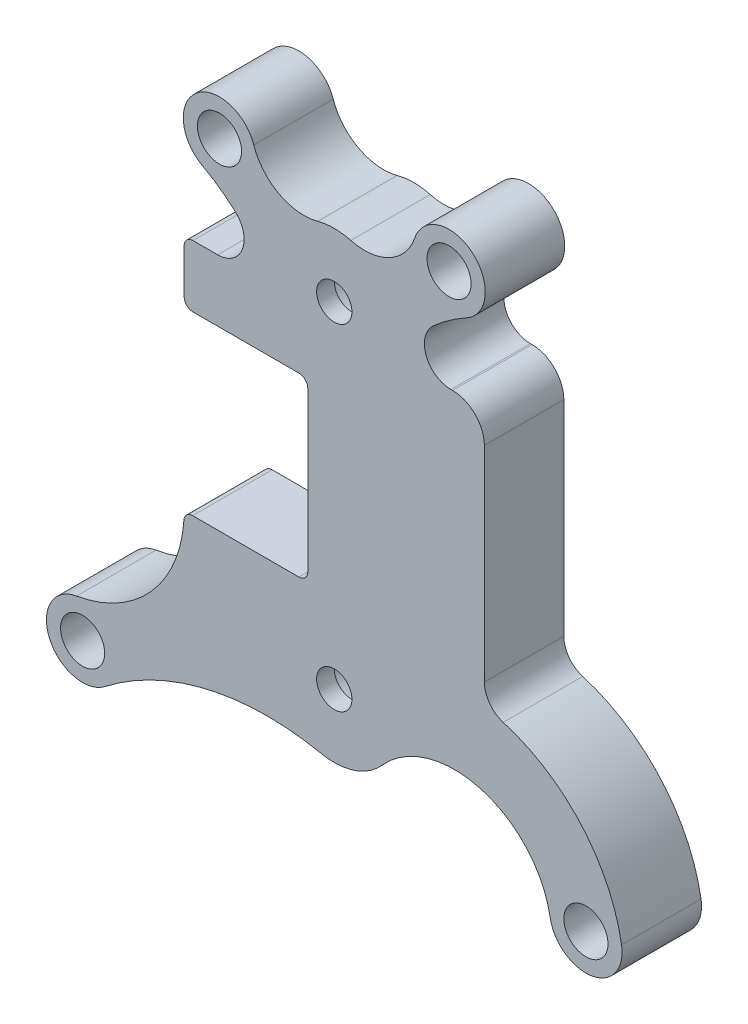
SolidWorks part; units mm, degrees
material "Полиамид ПА-6Б ТУ 6-05-988-87"
ref_plane "Спереди" through (0, 0, 0) normal (0, 0, 1) x (1, 0, 0)
ref_plane "Сверху" through (0, 0, 0) normal (0, 1, 0) x (1, 0, 0)
ref_plane "Справа" through (0, 0, 0) normal (1, 0, 0) x (0, 0, -1)
sketch "Эскиз1" plane through (0, 0, 0) normal (0, 0, 1) x (1, 0, 0)
  line L0 (0, 0) -> (17.2556, 0) construction
  line L1 (0, 0) -> (0, -0.75) construction
  line L2 (11.0974, -0.75) -> (-16.0026, -0.75) construction
  line L3 (-8.5, 8.5) -> (-2.75, 8.5) construction
  line L4 (-2, -5) -> (-8.016, -5)
  line L5 (-1.5, -4.5) -> (-1.5, 4.5)
  line L6 (-2, 5) -> (-8, 5)
  line L10 (-8, 8.5) -> (-6.6051, 8.5)
  line L11 (-8.5, 8) -> (-8.5, 5.5)
  line L13 (8.5, 6.7) -> (8.5, -4.9039)
  line L14 (6.0474, 13.15) -> (-10.9526, 13.15) construction
  line L16 (6.6051, 8.5) -> (6.7, 8.5)
  line L17 (0, 0) -> (-7.145, 0) construction
  arc A0 (7.4857, 12.4525) -> (4.5587, 14.9087) centre (6.5, 14.25) ccw
  circle A1 centre (6.5, 14.25) radius 1.25
  circle A2 centre (-6.5, 14.25) radius 1.25
  circle A3 centre (0, -9.5) radius 1
  arc A4 (-4.5587, 14.9087) -> (-7.4857, 12.4525) centre (-6.5, 14.25) ccw
  arc A5 (-14.5962, -12.2294) -> (-12.9918, -15.8684) centre (-14.25, -14.25) ccw
  circle A6 centre (-14.25, -14.25) radius 1.25
  circle A7 centre (14.25, -14.25) radius 1.25
  arc A8 (12.2299, -14.5991) -> (16.2701, -13.9009) centre (14.25, -14.25) ccw
  circle A9 centre (0, 9.5) radius 2 construction
  circle A10 centre (0, 9.5) radius 1
  arc A11 (0.937, 12.9759) -> (-0.937, 12.9759) centre (0, 9.5) ccw
  arc A12 (-4.5587, 14.9087) -> (-0.937, 12.9759) centre (-1.7178, 15.8725) ccw
  arc A13 (-7.4857, 12.4525) -> (-5.6012, 11.1145) centre (-12.2938, 3.6843) cw
  circle A14 centre (0, -9.5) radius 2 construction
  arc A15 (7.4857, 12.4525) -> (5.6012, 11.1145) centre (12.2938, 3.6843) ccw
  arc A16 (4.5587, 14.9087) -> (0.937, 12.9759) centre (1.7178, 15.8725) cw
  arc A17 (2.6942, -11.8878) -> (-0.7326, -13.0247) centre (0, -9.5) cw
  arc A18 (6.6051, 8.5) -> (5.6012, 11.1145) centre (6.6051, 10) cw
  arc A19 (2.6942, -11.8878) -> (12.2299, -14.5991) centre (6.8103, -15.5357) cw
  arc A20 (-6.6051, 8.5) -> (-5.6012, 11.1145) centre (-6.6051, 10) ccw
  arc A21 (16.2701, -13.9009) -> (9.569, -6.3406) centre (6.8103, -15.5357) ccw
  arc A22 (9.569, -6.3406) -> (8.5, -4.9039) centre (10, -4.9039) cw
  arc A23 (-12.9918, -15.8684) -> (-0.7326, -13.0247) centre (-3.7853, -27.7108) cw
  arc A24 (-14.5962, -12.2294) -> (-8.515, -5.4681) centre (-15.8348, -5) ccw
  arc A25 (-8, 8.5) -> (-8.5, 8) centre (-8, 8) ccw
  arc A26 (-8.515, -5.4681) -> (-8.016, -5) centre (-8.016, -5.5) cw
  arc A27 (-2, -5) -> (-1.5, -4.5) centre (-2, -4.5) ccw
  arc A28 (-1.5, 4.5) -> (-2, 5) centre (-2, 4.5) ccw
  arc A29 (-8, 5) -> (-8.5, 5.5) centre (-8, 5.5) cw
  arc A30 (6.7, 8.5) -> (8.5, 6.7) centre (6.7, 6.7) cw
  point P1 (-1.5, 0)
  point P20 (-8.5, 8.5)
  point P43 (-7.145, 0)
  point P44 (-8.5, -5)
  dimension "D1" = 2.5
  dimension "D2" = 0.8
  dimension "D3" = 4
  dimension "D4" = 2
  dimension "D5" = 1.6
  dimension "D6" = 3
  dimension "D7" = 10
  dimension "D8" = 5.5
  dimension "D11" = 1.5
  dimension "D12" = 15
  dimension "D13" = 8.5
  dimension "D14" = 0.5
  dimension "D15" = 1.8
  dimension "D9" = 10
  dimension "D10" = 1.5
extrude "Бобышка-Вытянуть3" add sketch "Эскиз1" along normal blind 4.5
sketch "Эскиз3" plane through (0, 0, 0) normal (0, 0, -1) x (-1, 0, 0)
  circle A0 centre (0, -9.5) radius 2 construction
  circle A1 centre (0, 9.5) radius 2 construction
  circle A2 centre (0, -9.5) radius 2
  circle A3 centre (0, 9.5) radius 2
extrude "Вырез-Вытянуть2" cut sketch "Эскиз3" against normal offset from surface (3.5 mm away) 1 up to face at (1, 9.5, 4.5)
sketch "Эскиз4" plane through (0, 0, 0) normal (0, 0, -1) x (-1, 0, 0)
  line L0 (6.35, -8.95) -> (4.55, -8.95)
  line L1 (-0.95, -3.0841) -> (-0.95, -16.25)
  line L2 (-0.95, -16.25) -> (6.35, -16.25)
  line L3 (6.35, -16.25) -> (6.35, -8.95)
  line L4 (5.35, -15.25) -> (5.35, -9.95)
  line L5 (0.05, -15.25) -> (5.35, -15.25)
  line L6 (0.05, -9.95) -> (0.05, -15.25)
  line L7 (5.35, -9.95) -> (0.05, -9.95)
  line L8 (5.35, -15.25) -> (5.35, -9.95) construction
  line L9 (0.05, -15.25) -> (5.35, -15.25) construction
  line L10 (0.05, -9.95) -> (0.05, -15.25) construction
  line L11 (5.35, -9.95) -> (0.05, -9.95) construction
  line L13 (0.1132, -3.0841) -> (-0.95, -3.0841)
  line L14 (0.1132, -3.0841) -> (0.1132, 2.9159)
  line L15 (1.1132, 3.9159) -> (8.7132, 3.9159)
  line L16 (-14.05, -4.95) -> (-14.05, -7.95)
  line L17 (-9.05, -4.95) -> (-14.05, -4.95)
  line L18 (-9.05, -7.95) -> (-9.05, -4.95)
  line L19 (-14.05, -7.95) -> (-9.05, -7.95)
  line L20 (-14.05, -4.95) -> (-14.05, -7.95)
  line L21 (-9.05, -4.95) -> (-14.05, -4.95)
  line L22 (-9.05, -7.45) -> (-9.05, -4.95)
  line L23 (-14.05, -7.95) -> (-9.55, -7.95)
  line L25 (3.55, -6.05) -> (0.55, -6.05)
  line L26 (-0.95, -8.95) -> (-0.95, -16.25) construction
  line L29 (4.55, -7.05) -> (4.55, -8.95)
  line L30 (8.7132, 4.4159) -> (8.7132, 3.9159)
  line L32 (6.35, -8.95) -> (-0.95, -8.95) construction
  line L33 (2.0026, -0.75) -> (4.0026, -0.75)
  line L34 (2.0026, -0.75) -> (4.0026, -0.75)
  line L35 (5.0026, -0.75) -> (7.0026, -0.75)
  line L36 (5.0026, -0.75) -> (7.0026, -0.75)
  arc A10 (0.1132, 2.9159) -> (1.1132, 3.9159) centre (1.1132, 2.9159) cw
  arc A11 (-9.05, -7.45) -> (-9.55, -7.95) centre (-9.55, -7.45) cw
  dimension "D7" = 1
  dimension "D8" = 0.5
  dimension "D4" = 7
  dimension "D5" = 0
  dimension "D1" = 0
  dimension "D2" = 1
  dimension "D3" = 0
  dimension "D6" = 0
extrude "Вырез-Вытянуть3" cut sketch "Эскиз4" against normal blind 3.5 rebuild error yes
fillet "Скругление1" radius 0.5 rebuild error yes
fillet "Скругление2" radius 0.5 rebuild error yes tangent propagation no
